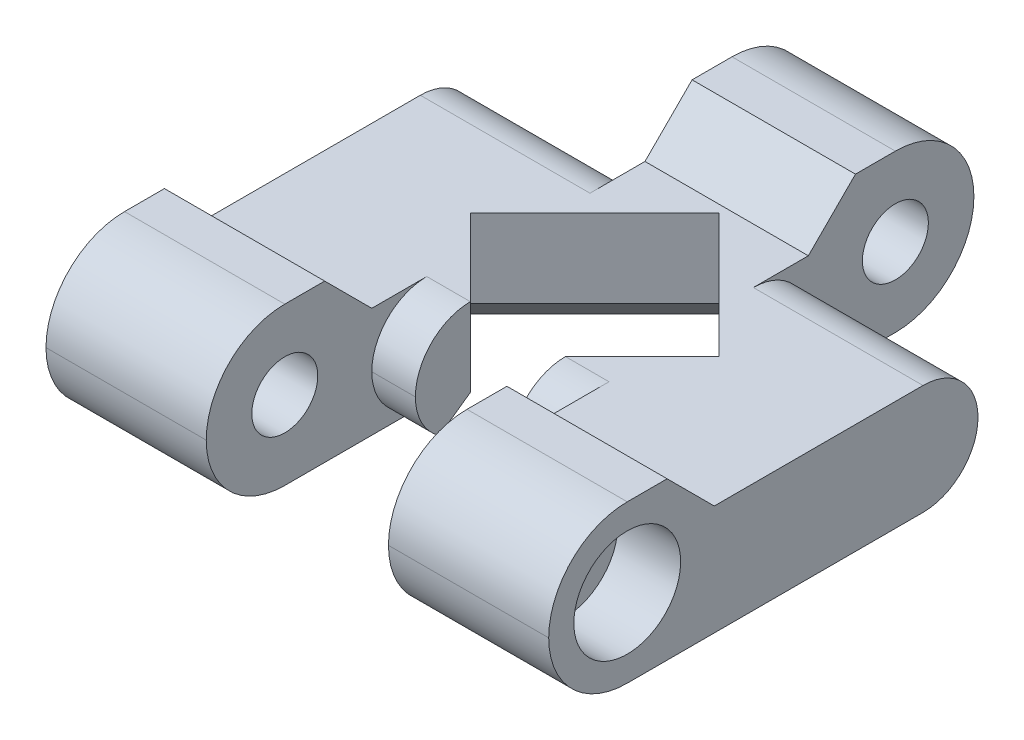
SolidWorks part; units mm, degrees
ref_plane "Спереди" through (0, 0, 0) normal (0, 0, 1) x (1, 0, 0)
ref_plane "Сверху" through (0, 0, 0) normal (0, 1, 0) x (1, 0, 0)
ref_plane "Справа" through (0, 0, 0) normal (1, 0, 0) x (0, 0, -1)
ref_plane "Plane1" through (0, 14.3201, 0) normal (0, 1, 0) x (1, 0, 0)
sketch "Sketch2" plane through (0, 0, 0) normal (-1, 0, 0) x (0, 0, 1)
  line L0 (0, -2.1068) -> (0, 20.3386) construction
  line L1 (0, 0) -> (9.4347, 22.7774) construction
  line L2 (0, 0) -> (-13.1904, 31.8444) construction
  line L4 (-11.0126, 16.8201) -> (16.1649, 16.8201) construction
  line L5 (6.5248, 14.3201) -> (-6.5248, 14.3201) construction
  circle A0 centre (6.9671, 16.8201) radius 0.95
  circle A1 centre (-6.9671, 16.8201) radius 0.95
  circle A3 centre (6.9671, 16.8201) radius 2.5
  circle A4 centre (-6.9671, 16.8201) radius 2.5
  dimension "D4" = 1.9
  dimension "D5" = 5
  dimension "D1" = 22.5
  dimension "D2" = 22.5
  dimension "D3" = 2.5
sketch "Sketch3" plane through (0, 0, 0) normal (-1, 0, 0) x (0, 0, 1)
  line L1 (-9.4671, 14.3201) -> (9.4671, 14.3201)
  line L2 (-9.4671, 14.3201) -> (-9.4671, 19.3201)
  line L3 (-9.4671, 19.3201) -> (9.4671, 19.3201)
  line L4 (9.4671, 14.3201) -> (9.4671, 19.3201)
extrude "Boss-Extrude1" add sketch "Sketch3" against normal blind 8
sketch "Sketch5" plane through (0, 0, 0) normal (-1, 0, 0) x (0, 0, 1)
  circle A0 centre (6.9671, 16.8201) radius 1.05
  circle A1 centre (-6.9671, 16.8201) radius 1.05
  dimension "D1" = 2.1
extrude "Cut-Extrude1" cut sketch "Sketch5" against normal up to next
sketch "Sketch4" plane through (0, 0, 0) normal (-1, 0, 0) x (0, 0, 1)
  line L0 (9.4671, 19.3201) -> (-9.4671, 19.3201) construction
  line L1 (9.4671, 14.3201) -> (4.1971, 14.3201)
  line L2 (9.4671, 14.3201) -> (9.4671, 19.3201)
  line L3 (9.4671, 19.3201) -> (4.1971, 19.3201)
  line L4 (4.1971, 14.3201) -> (4.1971, 19.3201)
  dimension "D1" = 5.27
extrude "Cut-Extrude2" cut sketch "Sketch4" against normal blind 2.9
sketch "Sketch6" plane through (8, 0, 0) normal (1, 0, 0) x (0, 0, -1)
  line L0 (6.5248, 14.3201) -> (-6.5248, 14.3201) construction
  line L1 (9.4671, 19.3201) -> (4.1971, 19.3201)
  line L2 (9.4671, 19.3201) -> (9.4671, 14.3201)
  line L3 (9.4671, 14.3201) -> (4.1971, 14.3201)
  line L4 (4.1971, 19.3201) -> (4.1971, 14.3201)
  dimension "D1" = 5.27
extrude "Cut-Extrude3" cut sketch "Sketch6" against normal blind 5.4
sketch "Sketch1" plane through (0, 14.3201, 0) normal (0, -1, 0) x (-1, 0, 0)
  line L0 (3.5355, 0) -> (0, -3.5355) construction
  line L1 (3.5355, 0) -> (0, 3.5355) construction
  line L2 (0, -3.5355) -> (-3.5355, 0) construction
  line L3 (0, 3.5355) -> (-3.5355, 0) construction
  line L4 (3.9598, 0) -> (0, -3.9598)
  line L5 (0, -3.9598) -> (-3.9598, 0)
  line L6 (0, 3.9598) -> (-3.9598, 0)
  line L7 (3.9598, 0) -> (0, 3.9598)
  line L8 (-16.1461, 0) -> (1.5759, 0) construction
  dimension "D2" = 5
  dimension "D3" = 5
extrude "Cut-Extrude5" cut sketch "Sketch1" against normal up to next
sketch "Sketch7" plane through (0, 0, 0) normal (-1, 0, 0) x (0, 0, 1)
  line L0 (-4.1971, 17.8201) -> (4.1971, 17.8201)
  line L1 (4.1971, 17.8201) -> (5.6971, 19.3201)
  line L2 (9.4671, 19.3201) -> (4.1971, 19.3201) construction
  line L3 (5.6971, 19.3201) -> (-5.6971, 19.3201)
  line L4 (-3.9598, 19.3201) -> (-9.4671, 19.3201) construction
  line L5 (-5.6971, 19.3201) -> (-4.1971, 17.8201)
  line L6 (0, -2.1068) -> (0, 20.3386) construction
  point P2 (0, 17.8201)
  dimension "D1" = 1.5
  dimension "D2" = 2.77
  dimension "D4" = 135
  dimension "D5" = 135
extrude "Cut-Extrude6" cut sketch "Sketch7" against normal up to next contours L3 L5 L0 L1
sketch "Sketch10" plane through (8, 0, 0) normal (1, 0, 0) x (0, 0, -1)
  circle A0 centre (-6.9671, 16.8201) radius 1.7
  dimension "D1" = 3.4
extrude "Cut-Extrude9" cut sketch "Sketch10" against normal blind 2
mirror "Mirror2" about plane through (0, 0, 0) normal (1, 0, 0) of bodies 114 108
fillet "Fillet1" radius 2.5 12 edges at (-5.45, 14.3201, 9.4671) (-2.9, 16.8201, 9.4671) (-2.6, 16.8201, -9.4671) (-5.45, 19.3201, 9.4671) (-8, 16.8201, 9.4671) (8, 16.8201, 9.4671) (2.9, 16.8201, 9.4671) (0, 14.3201, -9.4671) (0, 19.3201, -9.4671) (2.6, 16.8201, -9.4671) (5.45, 19.3201, 9.4671) (5.45, 14.3201, 9.4671)
fillet "Fillet2" radius 1.75 6 edges at (0, 14.3201, 4.1971) (0, 17.8201, 4.1971) (5.3, 14.3201, -4.1971) (5.3, 17.8201, -4.1971) (-5.3, 14.3201, -4.1971) (-5.3, 17.8201, -4.1971)
sketch "Sketch8" plane through (0, 14.3201, 0) normal (0, 1, 0) x (1, 0, 0)
  line L0 (2.9, -4.1971) -> (-2.9, -4.1971) construction
  line L1 (-1.5127, -2.4471) -> (1.5127, -2.4471)
  line L2 (-1.5127, -2.4471) -> (-1.5127, -4.1971)
  line L3 (-1.5127, -4.1971) -> (1.5127, -4.1971)
  line L4 (1.5127, -2.4471) -> (1.5127, -4.1971)
extrude "Cut-Extrude7" cut sketch "Sketch8" along normal up to next
chamfer "Chamfer1" distance 1 angle 45 4 edges at (-2.7362, 14.3201, 1.2236) (2.7362, 14.3201, 1.2236) (1.9799, 14.3201, -1.9799) (-1.9799, 14.3201, -1.9799)
